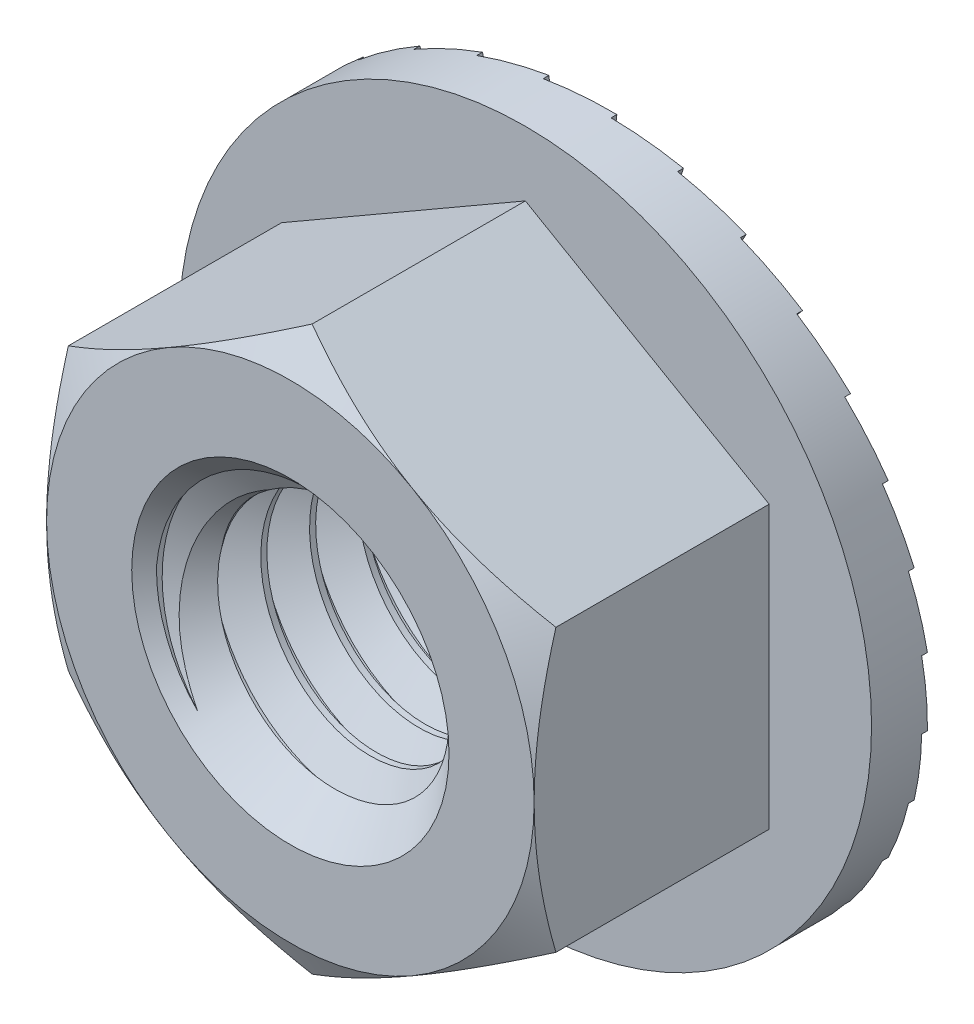
SolidWorks part; units mm, degrees
ref_plane "Front Plane" through (0, 0, 0) normal (0, 0, 1) x (1, 0, 0)
ref_plane "Top Plane" through (0, 0, 0) normal (0, 1, 0) x (1, 0, 0)
ref_plane "Right Plane" through (0, 0, 0) normal (1, 0, 0) x (0, 0, -1)
sketch "Sketch1" plane through (0, 0, 0) normal (0, 0, 1) x (1, 0, 0)
  line L1 (0, 5.7735) -> (-5, 2.8868)
  line L2 (-5, 2.8868) -> (-5, -2.8868)
  line L3 (-5, -2.8868) -> (0, -5.7735)
  line L4 (0, -5.7735) -> (5, -2.8868)
  line L5 (5, -2.8868) -> (5, 2.8868)
  line L6 (5, 2.8868) -> (0, 5.7735)
  circle A0 centre (0, 0) radius 5 construction
  dimension "Hex" = 10
extrude "Extrude1" add sketch "Sketch1" against normal blind 6
sketch "Sketch13" plane through (0, 0, -6) normal (0, 0, -1) x (-1, 0, 0)
  circle A0 centre (0, 0) radius 7.1
  dimension "Flange od" = 14.2
extrude "Extrude3" add sketch "Sketch13" against normal blind 1.18
sketch "Sketch2" plane through (0, 0, 0) normal (0, 0, 1) x (1, 0, 0)
  circle A0 centre (0, 0) radius 5 construction
  circle A1 centre (0, 0) radius 5
extrude "Cut-Extrude1" cut sketch "Sketch2" against normal through all draft 60 flip side to cut
sketch "Sketch4" plane through (0, 0, 0) normal (0, 0, 1) x (1, 0, 0)
  circle A0 centre (0, 0) radius 3
  dimension "Thread Dia" = 6
extrude "Cut-Extrude3" cut sketch "Sketch4" against normal through all
sketch "Sketch7" plane through (0, 0, 0) normal (0, 0, 1) x (1, 0, 0)
  circle A4 centre (0, 0) radius 3.254
  circle A5 centre (0, 0) radius 3.254
  dimension "D1" = 0.254
sketch "Sketch8" plane through (0, 0, -6) normal (0, 0, -1) x (-1, 0, 0)
  circle A1 centre (0, 0) radius 3.254
  circle A2 centre (0, 0) radius 3.254 construction
sketch "Sketch5" plane through (0, 0, 0) normal (0, 0, 1) x (1, 0, 0)
  circle A0 centre (0, 0) radius 3 construction
  circle A1 centre (0, 0) radius 3
curve "Helix/Spiral1" pitch 1 height 7 turns 7 parameters "pitch"=1
sketch "Sketch9" plane through (0, 0, 0) normal (1, 0, 0) x (0, 0, -1)
  line L0 (-0.5, 3) -> (-0.375, 3)
  line L1 (-0.375, 3) -> (0, 2.3505)
  line L2 (-0.5, 3) -> (-0.875, 2.3505)
  line L3 (-0.875, 2.3505) -> (0, 2.3505)
  line L4 (-0.4375, 3) -> (-0.4375, 2.3505) construction
  line L5 (-0.6875, 2.6752) -> (-0.1875, 2.6752) construction
  line L7 (0, 2.3505) -> (0, 3) construction
  line L8 (0, 3) -> (0, -3) construction
  dimension "D1" = 0.125
  dimension "D2" = 0.5
  dimension "D3" = 60
sketch "Sketch12" plane through (0, 0, 0) normal (0, 0, 1) x (1, 0, 0)
  circle A0 centre (0, 0) radius 2.3505
  circle A1 centre (0, 0) radius 3 construction
  circle A2 centre (0, 0) radius 3
extrude "Extrude2" add sketch "Sketch12" against normal up to surface (6 mm away)
sweep "Cut-Sweep1" cut profiles "Sketch9" path "Helix/Spiral1"
extrude "Cut-Extrude6" cut sketch "Sketch7" against normal through all draft 45
extrude "Cut-Extrude7" cut sketch "Sketch8" against normal through all draft 45
sketch "Sketch14" plane through (0, 0, -6) normal (0, 0, -1) x (-1, 0, 0)
  circle A4 centre (0, 0) radius 5.286
  circle A5 centre (0, 0) radius 5.286
  dimension "D1" = 2.032
extrude "Cut-Extrude8" cut sketch "Sketch14" against normal blind 0.118 flip side to cut
sketch "Sketch15" plane through (0, 0, -5.882) normal (0, 0, -1) x (-1, 0, 0)
  line L0 (-0.5181, 5.2605) -> (-0.6959, 7.0658)
  line L1 (0.5181, 5.2605) -> (0.6959, 7.0658)
  line L2 (0, 0) -> (0.5181, 5.2605) construction
  line L3 (0, 0) -> (-0.5181, 5.2605) construction
  circle A0 centre (0, 0) radius 7.1 construction
  circle A1 centre (0, 0) radius 5.286 construction
  arc A2 (0.6959, 7.0658) -> (-0.6959, 7.0658) centre (0, 0) ccw
  arc A3 (0.5181, 5.2605) -> (-0.5181, 5.2605) centre (0, 0) ccw
  dimension "D1" = 11.25
extrude "Extrude4" add sketch "Sketch15" along normal up to surface (0.118 mm away) separate body up to face at (-3.254, 0, -6)
sketch "Sketch16" plane through (0, 0, 0) normal (0, 1, 0) x (1, 0, 0)
  line L0 (-0.6959, 5.882) -> (0.6959, 6)
  line L4 (-0.6959, 5.882) -> (0.6959, 5.882)
  line L5 (0.6959, 5.882) -> (0.6959, 6)
  line L6 (0.6959, 6) -> (-0.6959, 6)
  line L7 (-0.6959, 6) -> (-0.6959, 5.882)
  line L8 (-0.6959, 5.882) -> (0.6959, 5.882) construction
  line L9 (0.6959, 5.882) -> (0.6959, 6) construction
  line L10 (0.6959, 6) -> (-0.6959, 6)
  line L11 (-0.6959, 6) -> (-0.6959, 5.882)
  dimension "D1" = 0
extrude "Cut-Extrude9" cut sketch "Sketch16" along normal through all
pattern_circular "CirPattern1" count 32 over 360 about axis through (0, 0, 0) along (0, 0, 1) of bodies 119
combine bodies "Combine1" operation type add bodies to combine 117 119 120 121 122 123 124 125 126 127 128 129 130 131 132 133 134 135 136 137 139 140 141 142 143 144 145 146 147 148 149 150 151
sketch "Sketch17" plane through (0, 0, 0) normal (1, 0, 0) x (0, 0, -1)
  line L0 (6, 7.1) -> (6, -7.1) construction
  line L1 (4.82, 7.1) -> (4.82, -7.1) construction
  dimension "D1" = 1.18
sketch "Sketch18" plane through (0, 0, -4.82) normal (0, 0, 1) x (1, 0, 0)
  circle A0 centre (0, 0) radius 7.1
  circle A1 centre (0, 0) radius 7.1 construction
equation "\"D2@Sketch9\" = \"pitch@Helix/Spiral1\"*.5"
equation "\"D3@Helix/Spiral1\" = \"pitch@Helix/Spiral1\"+\"Height@Extrude1\""
equation "\"D1@Sketch9\" = \"pitch@Helix/Spiral1\"*.125"
equation "\"D1@Cut-Extrude8\" = \"flange thickness@Extrude3\"*.1"
equation "\"D1@Sketch17\" = \"flange thickness@Extrude3\""
